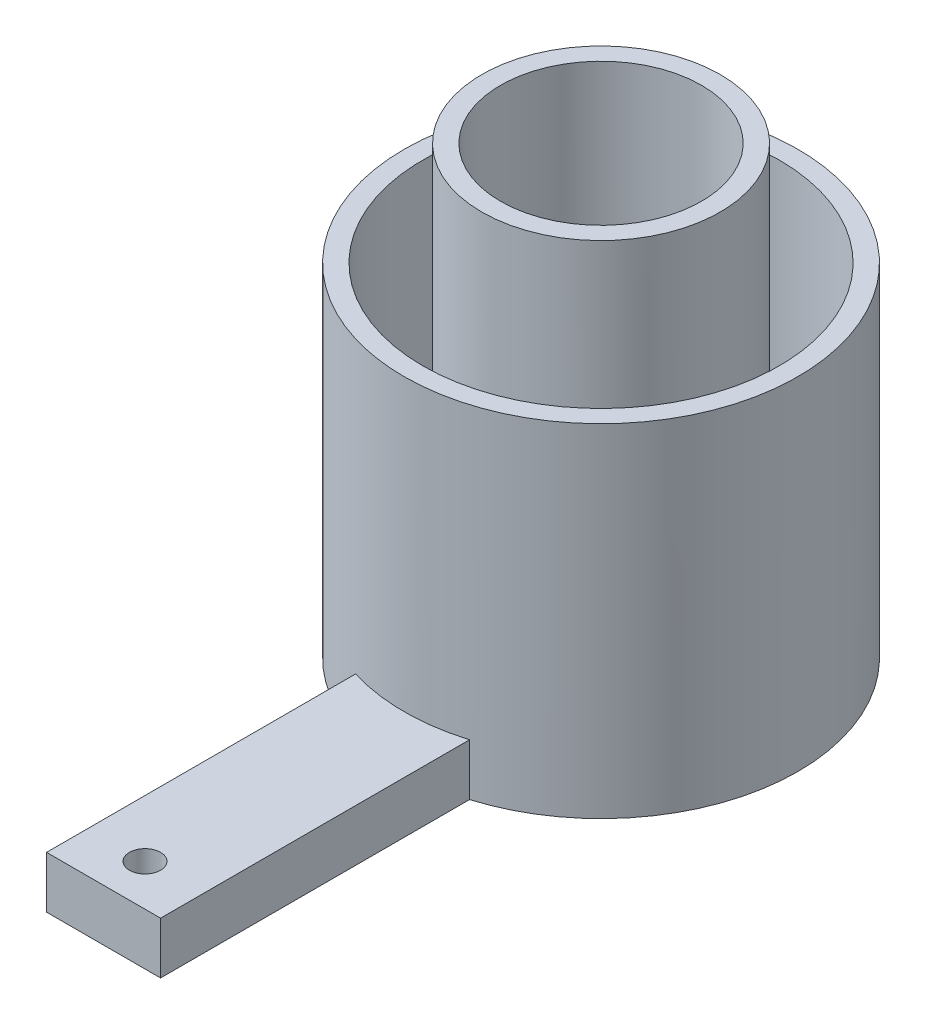
SolidWorks part; units mm, degrees
ref_plane "Front" through (0, 0, 0) normal (0, 0, 1) x (1, 0, 0)
ref_plane "Top" through (0, 0, 0) normal (0, 1, 0) x (1, 0, 0)
ref_plane "Right" through (0, 0, 0) normal (1, 0, 0) x (0, 0, -1)
sketch "Sketch1" plane through (0, 0, 0) normal (0, 1, 0) x (1, 0, 0)
  circle A0 centre (0, 0) radius 19
  circle A1 centre (0, 0) radius 17.2
  circle A2 centre (0, 0) radius 11.5
  circle A3 centre (0, 0) radius 9.7
  dimension "D1" = 38
  dimension "D3" = 23
  dimension "D2" = 1.8
  dimension "D4" = 1.8
extrude "Boss-Extrude1" add sketch "Sketch1" along normal blind 33 contours A0 A1 region at (-18.4626, 0, 0)
extrude "Boss-Extrude2" add sketch "Sketch1<3>" along normal blind 43 separate body contours A2 A3 region at (-11.1747, 0, 0)
sketch "Sketch1<3>" plane through (0, 0, 0) normal (0, 1, 0) x (1, 0, 0) same geometry as "Sketch1"
ref_plane "Plane1" through (0, 10, 0) normal (0, -1, 0) x (-1, 0, 0)
sketch "Sketch2" plane through (0, 10, 0) normal (0, -1, 0) x (-1, 0, 0)
  circle A0 centre (0, 0) radius 17.2 construction
  circle A1 centre (0, 0) radius 17.2
extrude "Boss-Extrude3" add sketch "Sketch2" against normal blind 3
sketch "Sketch3" plane through (0, 0, 0) normal (0, -1, 0) x (1, 0, 0)
  line L0 (-14.9219, -11.7616) -> (-5.1525, -5.0602)
  line L1 (-5.1525, -5.0602) -> (-3.5655, -6.2803)
  line L2 (-3.5655, -6.2803) -> (-7.53, -17.4442)
  line L3 (0, 0) -> (-4.359, -5.6702) construction
  circle A0 centre (0, 0) radius 19 construction
  arc A2 (-14.9219, -11.7616) -> (-7.53, -17.4442) centre (0, 0) ccw
  dimension "D1" = 108
  dimension "D2" = 108
extrude "Boss-Extrude4" add sketch "Sketch3" against normal blind 2.4
sketch "Sketch4" plane through (0, 0, 0) normal (0, -1, 0) x (1, 0, 0)
  line L1 (-5.5, 6) -> (5.5, 6)
  line L2 (-5.5, 6) -> (-5.5, 48)
  line L3 (-5.5, 48) -> (5.5, 48)
  line L4 (5.5, 6) -> (5.5, 48)
  line L5 (-5.5, 6) -> (5.5, 48) construction
  line L6 (-5.5, 48) -> (5.5, 6) construction
  circle A0 centre (0, 0) radius 9.7 construction
  circle A1 centre (0, 0) radius 9.7
  point P0 (0, 27)
  arc M5 (-13.434, -10.741) -> (-6.9262, -15.7438) centre (0, 0) cw
  circle M6 centre (0, 0) radius 19
  arc M8 (-5.011, -10.3508) -> (-8.7146, -7.5037) centre (0, 0) ccw
  arc M10 (-7.2196, -6.4782) -> (-4.4043, -8.6424) centre (0, 0) cw
  dimension "D1" = 42
  dimension "D2" = 11
  dimension "D3" = 6
extrude "Boss-Extrude5" add sketch "Sketch4" against normal blind 5 contours L4 L2 M8 M5 | L4 L2 M5 M6 | L4 L3 L2 M6 | L4 L2 M10 M8 region at (0, 0, 10.077) region at (0, 0, 13.9652) region at (0, 0, 17.813) region at (0, 0, 33.3646)
sketch "Sketch5" plane through (0, 0, 0) normal (0, -1, 0) x (1, 0, 0)
  line L1 (-5.5, 48) -> (5.5, 48) construction
  circle A0 centre (0, 44) radius 1.5
  dimension "D1" = 3
  dimension "D2" = 4
extrude "Cut-Extrude1" cut sketch "Sketch5" against normal through all
